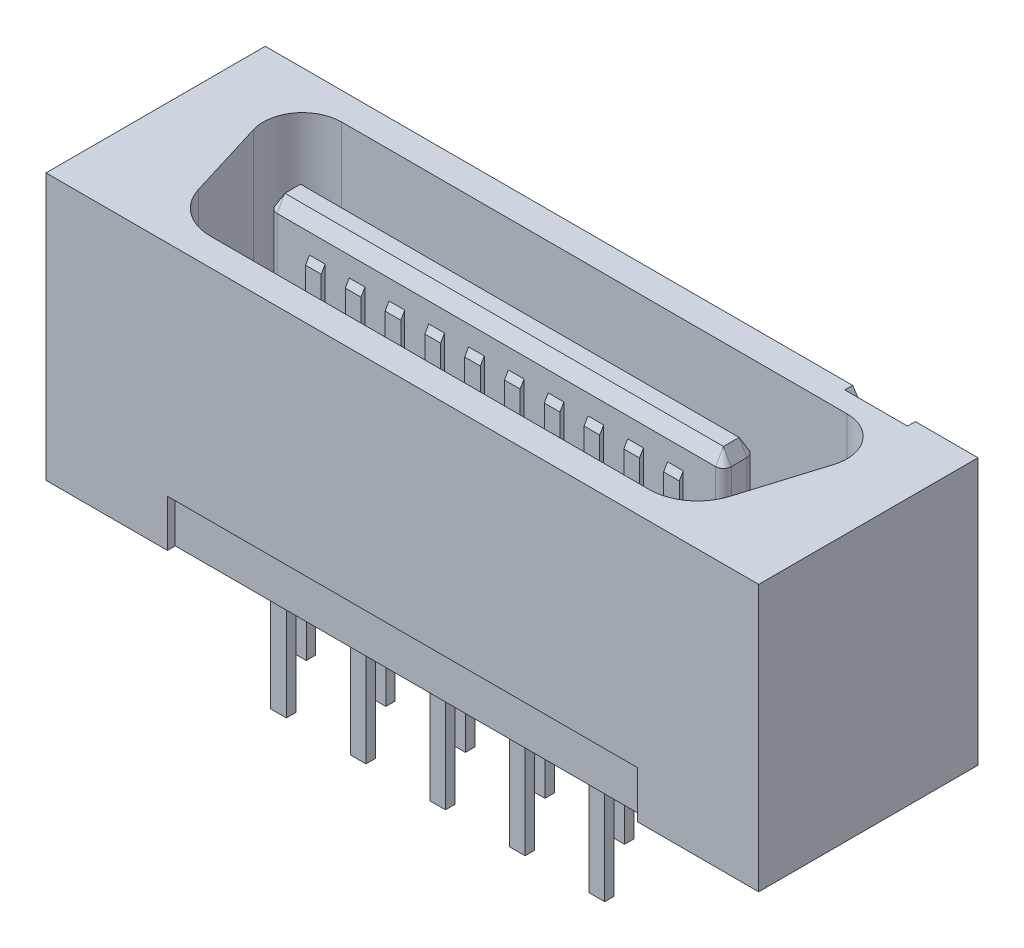
SolidWorks part; units mm, degrees
ref_plane "Front Plane" through (0, 0, 0) normal (0, 0, 1) x (1, 0, 0)
ref_plane "Top Plane" through (0, 0, 0) normal (0, 1, 0) x (1, 0, 0)
ref_plane "Right Plane" through (0, 0, 0) normal (1, 0, 0) x (0, 0, -1)
ref_axis "Axis1" through (0, 0, -88.99) along (0, 0, 1)
ref_axis "Axis2" through (0, -55, 0) along (0, 1, 0)
ref_axis "Axis3" through (-88.99, 0, 0) along (1, 0, 0)
sketch "Sketch1" plane through (0, 0, 0) normal (0, 1, 0) x (1, 0, 0)
  line L1 (11.375, -3.5) -> (-11.375, -3.5)
  line L2 (11.375, -3.5) -> (11.375, 3.5)
  line L3 (11.375, 3.5) -> (-11.375, 3.5)
  line L4 (-11.375, -3.5) -> (-11.375, 3.5)
  line L5 (11.375, -3.5) -> (-11.375, 3.5) construction
  line L6 (11.375, 3.5) -> (-11.375, -3.5) construction
  point P0 (0, 0)
  dimension "D1" = 22.75
  dimension "D2" = 7
extrude "Boss-Extrude1" add sketch "Sketch1" along normal blind 8.5
sketch "Sketch2" plane through (0, 0, -3.5) normal (0, 0, 1) x (1, 0, 0)
  line L0 (7.375, 8.5) -> (8.375, 7)
  line L1 (-11.375, 8.5) -> (11.375, 8.5) construction
  line L2 (8.375, 7) -> (9.375, 8.5)
  line L3 (9.375, 8.5) -> (7.375, 8.5)
  line L4 (8.375, 7) -> (8.375, 8.5) construction
  line L5 (11.375, 8.5) -> (11.375, 0) construction
  dimension "D1" = 2
  dimension "D2" = 1.5
  dimension "D3" = 3
extrude "Cut-Extrude1" cut sketch "Sketch2" along normal blind 0.25
sketch "Sketch3" plane through (0, 0, 0) normal (0, -1, 0) x (1, 0, 0)
  line L0 (-5.715, 2.8575) -> (5.715, 2.8575) construction
  line L1 (0, 3.5) -> (0, -3.5) construction
  line L2 (-11.375, 3.5) -> (11.375, 3.5) construction
  line L3 (11.375, -3.5) -> (-11.375, -3.5) construction
  line L4 (-5.715, 2.8575) -> (-5.715, -2.8575) construction
  line L5 (-5.715, 0) -> (0, 0) construction
  line L7 (-5.465, 0.8025) -> (-5.965, 0.8025)
  line L8 (-5.465, 0.8025) -> (-5.465, 1.1025)
  line L9 (-5.465, 1.1025) -> (-5.965, 1.1025)
  line L10 (-5.965, 0.8025) -> (-5.965, 1.1025)
  line L11 (-5.465, 0.8025) -> (-5.965, 1.1025) construction
  line L12 (-5.465, 1.1025) -> (-5.965, 0.8025) construction
  line L13 (-4.195, 2.7075) -> (-4.695, 2.7075)
  line L14 (-4.195, 2.7075) -> (-4.195, 3.0075)
  line L15 (-4.195, 3.0075) -> (-4.695, 3.0075)
  line L16 (-4.695, 2.7075) -> (-4.695, 3.0075)
  line L17 (-4.195, 2.7075) -> (-4.695, 3.0075) construction
  line L18 (-4.195, 3.0075) -> (-4.695, 2.7075) construction
  circle A0 centre (-4.445, 2.8575) radius 0.4 construction
  circle A1 centre (-5.715, 0.9525) radius 0.4 construction
  point P11 (0, 2.8575)
  dimension "D1" = 0.8
  dimension "D2" = 1.27
  dimension "D3" = 1.905
  dimension "D4" = 11.43
  dimension "D5" = 5.715
  dimension "D6" = 0.5
  dimension "D7" = 0.3
extrude "Boss-Extrude2" add sketch "Sketch3" along normal blind 3.3
chamfer "Chamfer1" distance 0.075 angle 45 8 edges at (-4.195, -3.3, 2.8575) (-4.445, -3.3, 2.7075) (-4.695, -3.3, 2.8575) (-4.445, -3.3, 3.0075) (-5.465, -3.3, 0.9525) (-5.715, -3.3, 0.8025) (-5.965, -3.3, 0.9525) (-5.715, -3.3, 1.1025)
pattern_linear "LPattern1" count 5 spacing 2.54 along (1, 0, 0) count 2 spacing 3.81 along (0, 0, -1) of "Boss-Extrude2", "Chamfer1"
sketch "Sketch4" plane through (0, 8.5, 0) normal (0, 1, 0) x (1, 0, 0)
  line L0 (-8.065, 2.625) -> (8.065, 2.625)
  line L1 (9.2601, 1.0086) -> (8.4819, -1.5294)
  line L2 (7, -2.625) -> (-7, -2.625)
  line L3 (0, -2.625) -> (0, 2.625) construction
  line L4 (-9.2601, 1.0086) -> (-8.4819, -1.5294)
  line L5 (-4.695, 0.625) -> (-4.195, 0.625)
  line L6 (7, -0.5) -> (-7, -0.5)
  line L7 (7.25, -0.25) -> (7.25, 0.25)
  line L8 (7, 0.5) -> (-7, 0.5)
  line L9 (-7.25, -0.25) -> (-7.25, 0.25)
  line L10 (7.25, -0.5) -> (-7.25, 0.5) construction
  line L11 (7.25, 0.5) -> (-7.25, -0.5) construction
  line L12 (-5.965, 0.375) -> (-5.465, 0.375)
  line L13 (-5.965, 0.375) -> (-5.965, 0.625)
  line L14 (-5.965, 0.625) -> (-5.465, 0.625)
  line L15 (-5.465, 0.375) -> (-5.465, 0.625)
  line L16 (-5.965, 0.375) -> (-5.465, 0.625) construction
  line L17 (-5.965, 0.625) -> (-5.465, 0.375) construction
  line L18 (-4.195, 0.375) -> (-4.195, 0.625)
  line L19 (-4.695, 0.375) -> (-4.195, 0.375)
  line L20 (-4.695, 0.375) -> (-4.695, 0.625)
  line L21 (-3.425, 0.625) -> (-2.925, 0.625)
  line L22 (-2.925, 0.375) -> (-2.925, 0.625)
  line L23 (-3.425, 0.375) -> (-2.925, 0.375)
  line L24 (-3.425, 0.375) -> (-3.425, 0.625)
  line L25 (-2.155, 0.625) -> (-1.655, 0.625)
  line L26 (-1.655, 0.375) -> (-1.655, 0.625)
  line L27 (-2.155, 0.375) -> (-1.655, 0.375)
  line L28 (-2.155, 0.375) -> (-2.155, 0.625)
  line L29 (-0.885, 0.625) -> (-0.385, 0.625)
  line L30 (-0.385, 0.375) -> (-0.385, 0.625)
  line L31 (-0.885, 0.375) -> (-0.385, 0.375)
  line L32 (-0.885, 0.375) -> (-0.885, 0.625)
  line L33 (0.385, 0.625) -> (0.885, 0.625)
  line L34 (0.885, 0.375) -> (0.885, 0.625)
  line L35 (0.385, 0.375) -> (0.885, 0.375)
  line L36 (0.385, 0.375) -> (0.385, 0.625)
  line L37 (1.655, 0.625) -> (2.155, 0.625)
  line L38 (2.155, 0.375) -> (2.155, 0.625)
  line L39 (1.655, 0.375) -> (2.155, 0.375)
  line L40 (1.655, 0.375) -> (1.655, 0.625)
  line L41 (2.925, 0.625) -> (3.425, 0.625)
  line L42 (3.425, 0.375) -> (3.425, 0.625)
  line L43 (2.925, 0.375) -> (3.425, 0.375)
  line L44 (2.925, 0.375) -> (2.925, 0.625)
  line L45 (4.195, 0.625) -> (4.695, 0.625)
  line L46 (4.695, 0.375) -> (4.695, 0.625)
  line L47 (4.195, 0.375) -> (4.695, 0.375)
  line L48 (4.195, 0.375) -> (4.195, 0.625)
  line L49 (5.465, 0.625) -> (5.965, 0.625)
  line L50 (5.965, 0.375) -> (5.965, 0.625)
  line L51 (5.465, 0.375) -> (5.965, 0.375)
  line L52 (5.465, 0.375) -> (5.465, 0.625)
  line L53 (-7.25, 0) -> (-5.965, 0) construction
  line L54 (7.25, 0) -> (5.965, 0) construction
  line L55 (5.465, -0.375) -> (5.465, -0.625)
  line L56 (5.465, -0.375) -> (5.965, -0.375)
  line L57 (5.965, -0.375) -> (5.965, -0.625)
  line L58 (5.465, -0.625) -> (5.965, -0.625)
  line L59 (4.195, -0.375) -> (4.195, -0.625)
  line L60 (4.195, -0.375) -> (4.695, -0.375)
  line L61 (4.695, -0.375) -> (4.695, -0.625)
  line L62 (4.195, -0.625) -> (4.695, -0.625)
  line L63 (2.925, -0.375) -> (2.925, -0.625)
  line L64 (2.925, -0.375) -> (3.425, -0.375)
  line L65 (3.425, -0.375) -> (3.425, -0.625)
  line L66 (2.925, -0.625) -> (3.425, -0.625)
  line L67 (1.655, -0.375) -> (1.655, -0.625)
  line L68 (1.655, -0.375) -> (2.155, -0.375)
  line L69 (2.155, -0.375) -> (2.155, -0.625)
  line L70 (1.655, -0.625) -> (2.155, -0.625)
  line L71 (0.385, -0.375) -> (0.385, -0.625)
  line L72 (0.385, -0.375) -> (0.885, -0.375)
  line L73 (0.885, -0.375) -> (0.885, -0.625)
  line L74 (0.385, -0.625) -> (0.885, -0.625)
  line L75 (-0.885, -0.375) -> (-0.885, -0.625)
  line L76 (-0.885, -0.375) -> (-0.385, -0.375)
  line L77 (-0.385, -0.375) -> (-0.385, -0.625)
  line L78 (-0.885, -0.625) -> (-0.385, -0.625)
  line L79 (-2.155, -0.375) -> (-2.155, -0.625)
  line L80 (-2.155, -0.375) -> (-1.655, -0.375)
  line L81 (-1.655, -0.375) -> (-1.655, -0.625)
  line L82 (-2.155, -0.625) -> (-1.655, -0.625)
  line L83 (-3.425, -0.375) -> (-3.425, -0.625)
  line L84 (-3.425, -0.375) -> (-2.925, -0.375)
  line L85 (-2.925, -0.375) -> (-2.925, -0.625)
  line L86 (-3.425, -0.625) -> (-2.925, -0.625)
  line L87 (-4.695, -0.375) -> (-4.695, -0.625)
  line L88 (-4.695, -0.375) -> (-4.195, -0.375)
  line L89 (-4.195, -0.375) -> (-4.195, -0.625)
  line L90 (-4.695, -0.625) -> (-4.195, -0.625)
  line L91 (-5.965, -0.375) -> (-5.965, -0.625)
  line L92 (-5.965, -0.375) -> (-5.465, -0.375)
  line L93 (-5.465, -0.375) -> (-5.465, -0.625)
  line L94 (-5.965, -0.625) -> (-5.465, -0.625)
  line L95 (-5.465, 0.5) -> (-4.695, 0.5) construction
  arc A0 (8.4819, -1.5294) -> (7, -2.625) centre (7, -1.075) cw
  arc A1 (8.065, 2.625) -> (9.2601, 1.0086) centre (8.065, 1.375) cw
  arc A2 (-8.4819, -1.5294) -> (-7, -2.625) centre (-7, -1.075) ccw
  arc A3 (-8.065, 2.625) -> (-9.2601, 1.0086) centre (-8.065, 1.375) ccw
  arc A4 (7.25, 0.25) -> (7, 0.5) centre (7, 0.25) ccw
  arc A5 (7, -0.5) -> (7.25, -0.25) centre (7, -0.25) ccw
  arc A6 (-7, -0.5) -> (-7.25, -0.25) centre (-7, -0.25) cw
  arc A7 (-7, 0.5) -> (-7.25, 0.25) centre (-7, 0.25) ccw
  point P15 (0, 0)
  point P32 (-5.715, 0.5)
  point P118 (-4.445, 0.375)
  point P120 (-5.715, 0.375)
  dimension "D5" = 0.25
  dimension "D12" = 1.25
  dimension "D13" = 1.55
  dimension "D2" = 16.13
  dimension "D3" = 14
  dimension "D4" = 5.25
  dimension "D6" = 14
  dimension "D7" = 1
  dimension "D8" = 0.5
  dimension "D10" = 0.25
  dimension "D11" = 1.27
  dimension "D9" = 10
extrude "Cut-Extrude3" cut sketch "Sketch4" against normal blind 7 contours L0 A3 L4 A2 L2 A0 L1 A1 A7 L8 A4 L7 A5 L6 A6 L9 region at (0, 8.5, -2.4314)
sketch "Sketch5" plane through (0, 8.5, 0) normal (0, 1, 0) x (1, 0, 0)
  line L0 (-5.965, 0.625) -> (-5.465, 0.625) construction
  line L1 (7, -0.5) -> (-7, -0.5)
  line L2 (7.25, -0.25) -> (7.25, 0.25)
  line L3 (7, 0.5) -> (-7, 0.5)
  line L4 (-7.25, -0.25) -> (-7.25, 0.25)
  line L5 (7.25, -0.5) -> (-7.25, 0.5) construction
  line L6 (7.25, 0.5) -> (-7.25, -0.5) construction
  line L7 (7.5, -0.625) -> (-7.5, -0.625)
  line L8 (7.5, -0.625) -> (7.5, 0.625)
  line L9 (7.5, 0.625) -> (-7.5, 0.625)
  line L10 (-7.5, -0.625) -> (-7.5, 0.625)
  line L11 (7.5, -0.625) -> (-7.5, 0.625) construction
  line L12 (7.5, 0.625) -> (-7.5, -0.625) construction
  arc A0 (7.25, 0.25) -> (7, 0.5) centre (7, 0.25) ccw
  arc A1 (7, -0.5) -> (7.25, -0.25) centre (7, -0.25) ccw
  arc A2 (-7, 0.5) -> (-7.25, 0.25) centre (-7, 0.25) ccw
  arc A3 (-7, -0.5) -> (-7.25, -0.25) centre (-7, -0.25) cw
  arc A5 (-7, 0.5) -> (-7.25, 0.25) centre (-7, 0.25) ccw construction
  point P0 (0, 0)
  point P21 (0, 0)
  dimension "D1" = 0.25
  dimension "D2" = 0.25
extrude "Cut-Extrude4" cut sketch "Sketch5" against normal blind 1.5
chamfer "Chamfer2" distance 0.25 angle 60 8 edges at (0, 8.5, -0.5) (7.1768, 8.5, -0.4268) (-7.1768, 8.5, -0.4268) (7.25, 8.5, 0) (-7.25, 8.5, 0) (7.1768, 8.5, 0.4268) (-7.1768, 8.5, 0.4268) (0, 8.5, 0.5) first distance on face at (0, 8.5, 0)
chamfer "Chamfer3" distance 0.25 angle 60 20 edges at (-5.715, 7, -0.5) (-4.445, 7, -0.5) (-3.175, 7, -0.5) (-1.905, 7, -0.5) (-0.635, 7, -0.5) (0.635, 7, -0.5) (1.905, 7, -0.5) (3.175, 7, -0.5) (4.445, 7, -0.5) (5.715, 7, -0.5) (5.715, 7, 0.5) (4.445, 7, 0.5) (3.175, 7, 0.5) (1.905, 7, 0.5) (0.635, 7, 0.5) (-0.635, 7, 0.5) (-1.905, 7, 0.5) (-3.175, 7, 0.5) (-4.445, 7, 0.5) (-5.715, 7, 0.5) first distance on face at (-5.715, 7, -0.5625) first distance on face at (-4.445, 7, -0.5625) first distance on face at (-3.175, 7, -0.5625) first distance on face at (-1.905, 7, -0.5625) first distance on face at (-0.635, 7, -0.5625) first distance on face at (0.635, 7, -0.5625) first distance on face at (1.905, 7, -0.5625) first distance on face at (3.175, 7, -0.5625) first distance on face at (4.445, 7, -0.5625) first distance on face at (5.715, 7, -0.5625) first distance on face at (5.715, 7, 0.5625) first distance on face at (4.445, 7, 0.5625) first distance on face at (3.175, 7, 0.5625) first distance on face at (1.905, 7, 0.5625) first distance on face at (0.635, 7, 0.5625) first distance on face at (-0.635, 7, 0.5625) first distance on face at (-1.905, 7, 0.5625) first distance on face at (-3.175, 7, 0.5625) first distance on face at (-4.445, 7, 0.5625) first distance on face at (-5.715, 7, 0.5625)
sketch "Sketch6" plane through (0, 0, 0) normal (0, -1, 0) x (1, 0, 0)
  line L0 (-11.375, 3.5) -> (11.375, 3.5) construction
  line L1 (-7.5, 3.5) -> (7.5, 3.5)
  line L2 (-7.5, 3.5) -> (-7.5, 3.25)
  line L3 (-7.5, 3.25) -> (7.5, 3.25)
  line L4 (7.5, 3.5) -> (7.5, 3.25)
  line L5 (0, 0) -> (-11.375, 0) construction
  line L6 (-11.375, -3.5) -> (-11.375, 3.5) construction
  line L7 (0, 0) -> (0, 3.25) construction
  line L8 (7.5, -3.5) -> (7.5, -3.25)
  line L9 (-7.5, -3.25) -> (7.5, -3.25)
  line L10 (-7.5, -3.5) -> (-7.5, -3.25)
  line L11 (-7.5, -3.5) -> (7.5, -3.5)
  dimension "D1" = 0.25
  dimension "D2" = 15
extrude "Cut-Extrude5" cut sketch "Sketch6" against normal blind 1.5
equation "\"D5@Sketch3\"=\"D3@Sketch3\"*3"
equation "\"D3@LPattern1\"=\"D2@Sketch3\"*2"
equation "\"D4@LPattern1\"=\"D3@Sketch3\"*2"
